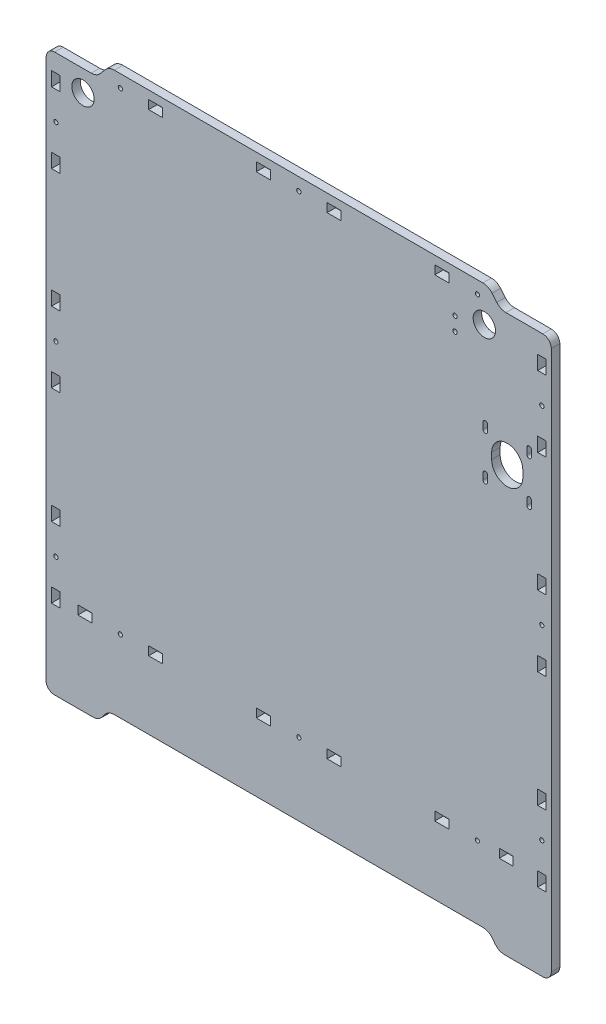
SolidWorks part; units mm, degrees
ref_plane "Спереди" through (0, 0, 0) normal (0, 0, 1) x (1, 0, 0)
ref_plane "Сверху" through (0, 0, 0) normal (0, 1, 0) x (1, 0, 0)
ref_plane "Справа" through (0, 0, 0) normal (1, 0, 0) x (0, 0, -1)
sketch "Эскиз1" plane through (0, 0, 0) normal (0, 0, 1) x (1, 0, 0)
  line L0 (133.6555, 83.4698) -> (133.6555, 87.9698)
  line L1 (133.6555, 118.9698) -> (133.6555, 114.4698)
  line L2 (130.4555, 83.4698) -> (130.4555, 87.9698)
  line L3 (158.5555, 98.9698) -> (158.5555, 103.4698)
  line L4 (130.4555, 118.9698) -> (130.4555, 114.4698)
  line L5 (161.4555, 118.9698) -> (161.4555, 114.4698)
  line L6 (164.6555, 118.9698) -> (164.6555, 114.4698)
  line L7 (136.5555, 98.9698) -> (136.5555, 103.4698)
  line L8 (161.4555, 83.4698) -> (161.4555, 87.9698)
  line L9 (164.6555, 83.4698) -> (164.6555, 87.9698)
  line L10 (-174.3451, 37.3796) -> (-174.3451, 47.3796)
  line L11 (106.3726, -142.2004) -> (96.3778, -142.2004)
  line L12 (96.3778, -142.2004) -> (96.3778, -136.0006)
  line L13 (96.3778, -136.0006) -> (106.3726, -136.0006)
  line L14 (106.3726, -136.0006) -> (106.3726, -142.2004)
  line L15 (151.7592, -142.2004) -> (141.91, -142.2004)
  line L16 (141.91, -142.2004) -> (141.91, -136.0006)
  line L17 (141.91, -136.0006) -> (151.7592, -136.0006)
  line L18 (151.7592, -136.0006) -> (151.7592, -142.2004)
  line L19 (-19.7199, 191.9054) -> (-29.6916, 191.9054)
  line L20 (-29.6916, 191.9054) -> (-29.6916, 198.1051)
  line L21 (-29.6916, 198.1051) -> (-19.7199, 198.1051)
  line L22 (-19.7199, 198.1051) -> (-19.7199, 191.9054)
  line L23 (30.2801, 191.9054) -> (20.3037, 191.9054)
  line L24 (20.3037, 191.9054) -> (20.3037, 198.1051)
  line L25 (20.3037, 198.1051) -> (30.2801, 198.1051)
  line L26 (30.2801, 198.1051) -> (30.2801, 191.9054)
  line L27 (-145.8164, -142.2004) -> (-155.6656, -142.2004)
  line L28 (-155.6656, -142.2004) -> (-155.6656, -136.0006)
  line L29 (-155.6656, -136.0006) -> (-145.8164, -136.0006)
  line L30 (-145.8164, -136.0006) -> (-145.8164, -142.2004)
  line L31 (-95.8164, -142.2004) -> (-105.7664, -142.2004)
  line L32 (-105.7664, -142.2004) -> (-105.7664, -136.0006)
  line L33 (-105.7664, -136.0006) -> (-95.8164, -136.0006)
  line L34 (-95.8164, -136.0006) -> (-95.8164, -142.2004)
  line L35 (-19.722, -142.199) -> (-29.6916, -142.199)
  line L36 (-29.6916, -142.199) -> (-29.6916, -135.9992)
  line L37 (-29.6916, -135.9992) -> (-19.722, -135.9992)
  line L38 (-19.722, -135.9992) -> (-19.722, -142.199)
  line L39 (30.2781, -142.199) -> (20.3037, -142.199)
  line L40 (20.3037, -142.199) -> (20.3037, -135.9992)
  line L41 (20.3037, -135.9992) -> (30.2781, -135.9992)
  line L42 (30.2781, -135.9992) -> (30.2781, -142.199)
  line L43 (-174.3451, 47.3796) -> (-168.3451, 47.3796)
  line L44 (-168.3451, 47.3796) -> (-168.3451, 37.3796)
  line L45 (-168.3451, 37.3796) -> (-174.3451, 37.3796)
  line L46 (-174.4387, -12.6115) -> (-174.4387, -2.6115)
  line L47 (-174.4387, -2.6115) -> (-168.4387, -2.6283)
  line L48 (-168.4387, -2.6283) -> (-168.4387, -12.6115)
  line L49 (-168.4387, -12.6115) -> (-174.4387, -12.6115)
  line L50 (-174.3451, 171.5396) -> (-174.3451, 181.5396)
  line L51 (-174.3451, 181.5396) -> (-168.3451, 181.5396)
  line L52 (-168.3451, 181.5396) -> (-168.3451, 171.5396)
  line L53 (-168.3451, 171.5396) -> (-174.3451, 171.5396)
  line L54 (-174.3451, 121.5396) -> (-174.3451, 131.5396)
  line L55 (-174.3451, 131.5396) -> (-168.3451, 131.5396)
  line L56 (-168.3451, 131.5396) -> (-168.3451, 121.5396)
  line L57 (-168.3451, 121.5396) -> (-174.3451, 121.5396)
  line L58 (-174.4387, -94.3415) -> (-174.4387, -84.3415)
  line L59 (-174.4387, -84.3415) -> (-168.4387, -84.3415)
  line L62 (-174.4387, -144.3199) -> (-174.4387, -134.3199)
  line L63 (-174.4387, -134.3199) -> (-168.4387, -134.3419)
  line L64 (-168.4387, -134.3419) -> (-168.4387, -144.3199)
  line L65 (-168.4387, -144.3199) -> (-174.4387, -144.3199)
  line L66 (169.0555, 35.4216) -> (169.0555, 45.4216)
  line L67 (169.0555, 45.4216) -> (175.077, 45.4216)
  line L68 (175.077, 45.4216) -> (175.077, 35.4216)
  line L69 (175.077, 35.4216) -> (169.0555, 35.4216)
  line L70 (169.0555, -14.5784) -> (169.0555, -4.5784)
  line L71 (169.0555, -4.5784) -> (175.077, -4.5784)
  line L72 (175.077, -4.5784) -> (175.077, -14.5784)
  line L73 (175.077, -14.5784) -> (169.0555, -14.5784)
  line L74 (169.0555, -96.2996) -> (169.0555, -86.2996)
  line L75 (169.0555, -86.2996) -> (175.077, -86.2996)
  line L76 (175.077, -86.2996) -> (175.077, -96.2996)
  line L77 (175.077, -96.2996) -> (169.0555, -96.2996)
  line L78 (169.0555, -146.2996) -> (169.0555, -136.2996)
  line L79 (169.0555, -136.2996) -> (175.077, -136.2996)
  line L80 (175.077, -136.2996) -> (175.077, -146.2996)
  line L81 (175.077, -146.2996) -> (169.0555, -146.2996)
  line L82 (169.0555, 169.7437) -> (169.0555, 179.5931)
  line L83 (169.0555, 179.5931) -> (175.0673, 179.5931)
  line L84 (175.0673, 169.7437) -> (169.0555, 169.7437)
  line L85 (169.0555, 119.5932) -> (169.0555, 129.5932)
  line L86 (169.0555, 129.5932) -> (175.0673, 129.5932)
  line L87 (175.0673, 129.5932) -> (175.0673, 119.5932)
  line L88 (175.0673, 119.5932) -> (169.0555, 119.5932)
  line L89 (-105.7664, 198.1027) -> (-95.7933, 198.1027)
  line L90 (-95.7933, 198.1027) -> (-95.7933, 191.903)
  line L91 (-95.7933, 191.903) -> (-105.7664, 191.903)
  line L92 (-105.7664, 191.903) -> (-105.7664, 198.1027)
  line L93 (106.3778, 191.903) -> (106.177, 191.9198)
  line L94 (96.3778, 191.903) -> (96.3778, 198.1027)
  line L95 (106.3778, 198.1027) -> (106.3778, 191.903)
  line L96 (146.6406, 193.9392) -> (172.677, 193.9396)
  line L97 (106.177, 191.9198) -> (96.3778, 191.903)
  line L99 (-136.4794, 200.9033) -> (-139.7752, 196.9759)
  line L100 (130.322, 203.9396) -> (-129.968, 203.9396)
  line L101 (136.8334, 200.9033) -> (140.1292, 196.9755)
  line L102 (175.077, 169.8198) -> (175.0673, 169.7437)
  line L103 (106.177, 198.1198) -> (106.3778, 198.1027)
  line L104 (96.3778, 198.1027) -> (106.177, 198.1198)
  line L105 (175.0673, 179.5931) -> (175.077, 169.8198)
  line L106 (139.1292, -196.3241) -> (136.8334, -193.3044)
  line L107 (-129.968, -190.2681) -> (130.322, -190.2681)
  line L108 (-172.323, -199.3604) -> (-145.2866, -199.3604)
  line L109 (-138.7752, -196.3241) -> (-136.4794, -193.3044)
  line L110 (172.677, -199.3604) -> (145.6406, -199.3604)
  line L111 (-178.0989, 187.9396) -> (-178.0989, -194.9959)
  line L112 (178.677, 187.9507) -> (178.677, -193.3604)
  line L113 (-174.4387, -94.3415) -> (-168.4387, -94.3415)
  line L114 (-168.4387, -94.3415) -> (-168.4387, -84.3415)
  line L115 (-172.0989, 193.9396) -> (-146.2866, 193.9396)
  arc A0 (158.5555, 103.4698) -> (136.5555, 103.4698) centre (147.5555, 103.4698) ccw
  arc A1 (161.4555, 83.4698) -> (164.6555, 83.4698) centre (163.0555, 83.4698) ccw
  arc A2 (136.5555, 98.9698) -> (158.5555, 98.9698) centre (147.5555, 98.9698) ccw
  arc A3 (130.4555, 83.4698) -> (133.6555, 83.4698) centre (132.0555, 83.4698) ccw
  arc A4 (164.6555, 87.9698) -> (161.4555, 87.9698) centre (163.0555, 87.9698) ccw
  circle A5 centre (110.677, 164.3198) radius 1.55
  circle A6 centre (110.677, 174.0198) radius 1.55
  arc A7 (130.4555, 114.4698) -> (133.6555, 114.4698) centre (132.0555, 114.4698) ccw
  arc A8 (133.6555, 118.9698) -> (130.4555, 118.9698) centre (132.0555, 118.9698) ccw
  arc A9 (164.6555, 118.9698) -> (161.4555, 118.9698) centre (163.0555, 118.9698) ccw
  arc A10 (161.4555, 114.4698) -> (164.6555, 114.4698) centre (163.0555, 114.4698) ccw
  arc A11 (133.6555, 87.9698) -> (130.4555, 87.9698) centre (132.0555, 87.9698) ccw
  circle A12 centre (131.377, 179.0198) radius 7.9
  circle A13 centre (-152.123, 179.0198) radius 7.9
  arc A14 (-129.968, 203.9396) -> (-136.4794, 200.9033) centre (-129.968, 195.4396) ccw
  arc A15 (-146.2866, 193.9396) -> (-139.7752, 196.9759) centre (-146.2866, 202.4396) ccw
  arc A17 (140.1292, 196.9755) -> (146.6406, 193.9392) centre (146.6406, 202.4392) ccw
  arc A18 (136.8334, 200.9033) -> (130.322, 203.9396) centre (130.322, 195.4396) ccw
  arc A19 (178.677, 187.9507) -> (172.677, 193.9396) centre (172.677, 187.9396) ccw
  arc A20 (136.8334, -193.3044) -> (130.322, -190.2681) centre (130.322, -198.7681) ccw
  arc A21 (-178.0989, -194.9959) -> (-172.323, -199.3604) centre (-172.3261, -193.3604) ccw
  arc A22 (-145.2866, -199.3604) -> (-138.7752, -196.3241) centre (-145.2866, -190.8604) ccw
  arc A23 (139.1292, -196.3241) -> (145.6406, -199.3604) centre (145.6406, -190.8604) ccw
  arc A24 (-129.968, -190.2681) -> (-136.4794, -193.3044) centre (-129.968, -198.7681) ccw
  circle A25 centre (-171.2415, 151.5396) radius 1.5
  arc A26 (172.677, -199.3604) -> (178.677, -193.3604) centre (172.677, -193.3604) ccw
  circle A27 centre (-171.2415, 17.3796) radius 1.5
  circle A28 centre (171.9877, 149.6742) radius 1.5
  circle A29 centre (126.4621, 195.0571) radius 1.5
  circle A30 centre (-125.7107, 195.0571) radius 1.5
  circle A31 centre (0.3581, 195.0571) radius 1.5
  circle A32 centre (-125.7495, -139.0659) radius 1.5
  circle A33 centre (-171.2415, -114.3215) radius 1.5
  circle A34 centre (0.3757, -139.0659) radius 1.5
  circle A35 centre (126.4428, -139.0659) radius 1.5
  circle A36 centre (171.9877, -116.2123) radius 1.5
  circle A37 centre (171.9877, 15.5093) radius 1.5
  arc A38 (-178.0989, 187.9396) -> (-172.0989, 193.9396) centre (-172.0989, 187.9396) cw
  dimension "D9" = 15.8
  dimension "D24" = 8.5
  dimension "D25" = 8.5
  dimension "D26" = 6
  dimension "D27" = 8.5
  dimension "D28" = 8.5
  dimension "D29" = 26.0364
  dimension "D30" = 6
  dimension "D32" = 12.4
  dimension "D3" = 10
  dimension "D4" = 20
  dimension "D5" = 20
  dimension "D6" = 10
  dimension "D7" = 6
  dimension "D8" = 6
  dimension "D10" = 74.16
  dimension "D11" = 10
  dimension "D12" = 6
  dimension "D13" = 20
  dimension "D14" = 20
  dimension "D15" = 10
  dimension "D16" = 71.73
  dimension "D17" = 6
  dimension "D18" = 10
  dimension "D19" = 20.01
  dimension "D20" = 10
  dimension "D21" = 6
  dimension "D22" = 403.3
  dimension "D23" = 19.98
  dimension "D31" = 8.3576
  dimension "D33" = 10
  dimension "D34" = 55.0404
extrude "Бобышка-Вытянуть1" add sketch "Эскиз1" along normal blind 6
